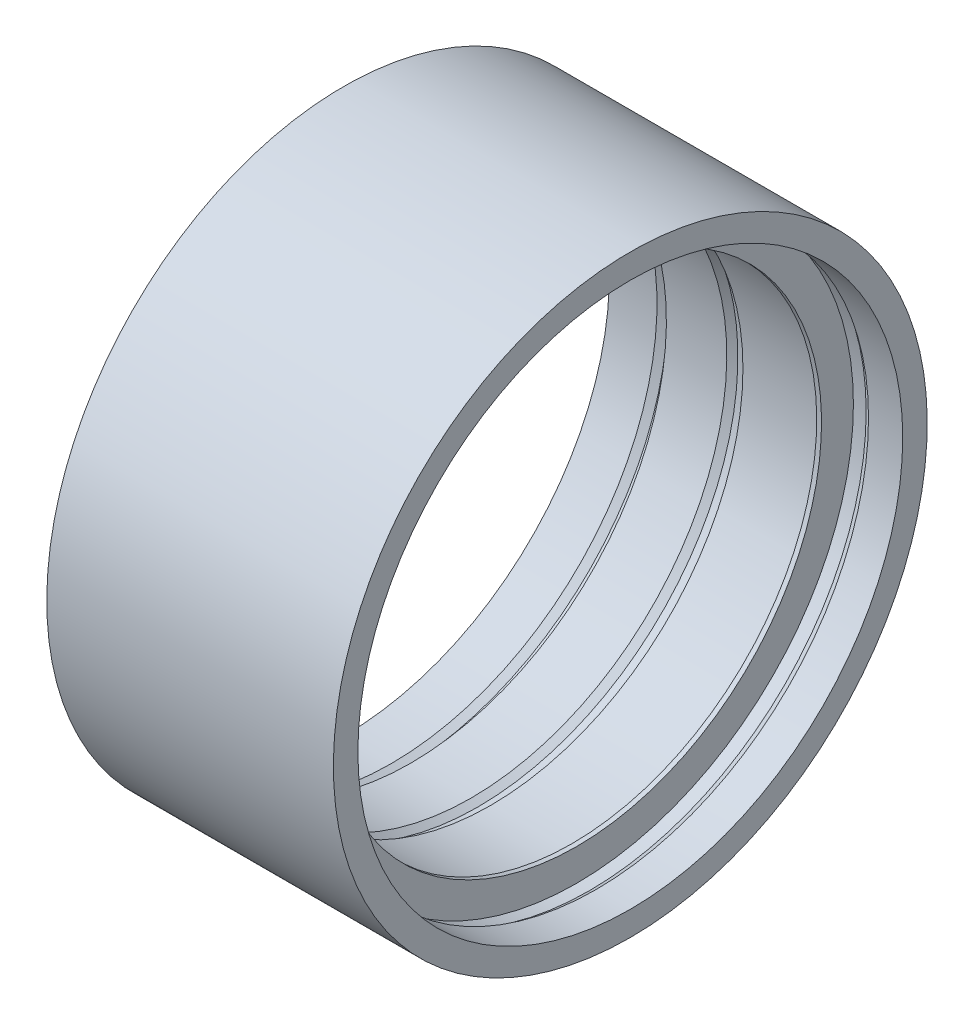
SolidWorks part; units mm, degrees
material "2018 slitina"
ref_plane "Přední rovina" through (0, 0, 0) normal (0, 0, 1) x (1, 0, 0)
ref_plane "Horní rovina" through (0, 0, 0) normal (0, 1, 0) x (1, 0, 0)
ref_plane "Pravá rovina" through (0, 0, 0) normal (1, 0, 0) x (0, 0, -1)
sketch "Skica2" plane through (0, 0, 0) normal (0, 0, 1) x (1, 0, 0)
  line L0 (-36.7133, -44.25) -> (6, -44.25)
  line L1 (6, -44.25) -> (6, -40.6)
  line L2 (6, -40.6) -> (0.9, -40.6)
  line L3 (-2, -36.5) -> (-2.7167, -36.5)
  line L4 (-2.7167, -36.5) -> (-2.8839, -37.6)
  line L5 (-2.8839, -37.6) -> (-14.8133, -37.6)
  line L6 (-14.8133, -37.6) -> (-14.8133, -38.75)
  line L7 (0, 0) -> (47.3772, 0) construction
  line L8 (-2, -36.5) -> (-2, -41.25)
  line L9 (-2, -41.25) -> (-0.1, -41.25)
  line L10 (-0.1, -41.25) -> (0.9, -40.6)
  line L11 (-14.8133, -38.75) -> (-16.7133, -38.75)
  line L12 (-16.7133, -38.75) -> (-17.7133, -38.094)
  line L13 (-17.7133, -38.094) -> (-26.7133, -38.094)
  line L14 (-26.7133, -38.094) -> (-26.7133, -40.25)
  line L15 (-26.7133, -40.25) -> (-28.6133, -40.25)
  line L16 (-28.6133, -40.25) -> (-29.6133, -39.594)
  line L17 (-29.6133, -39.594) -> (-36.7133, -39.594)
  line L18 (-36.7133, -39.594) -> (-36.7133, -44.25)
  line L19 (6, -40.6) -> (19.622, -44.25) construction
  line L20 (19.622, -44.25) -> (6, -44.25) construction
  arc A0 (-2.8691, -37.5) -> (-2.8691, 37.5) centre (-246.5, 0) ccw construction
  arc A1 (-2.8691, -37.5) -> (-2.8691, 37.5) centre (-246.5, 0) ccw construction
  point P0 (-15.7633, -38.75)
  point P11 (-2.8003, -37.05)
  dimension "D6" = 6
  dimension "D1" = 0.1
  dimension "D2" = 81.2
  dimension "D3" = 82.5
  dimension "D4" = 1.9
  dimension "D5" = 2.9
  dimension "D7" = 8
  dimension "D8" = 73
  dimension "D9" = 1.9
  dimension "D10" = 2.9
  dimension "D11" = 2
  dimension "D12" = 76.188
  dimension "D13" = 11
  dimension "D14" = 77.5
  dimension "D15" = 1.9
  dimension "D16" = 2.9
  dimension "D17" = 10
  dimension "D18" = 80.5
  dimension "D19" = 79.188
  dimension "D20" = 4
  dimension "D21" = 15
revolve "Rotovat1" add sketch "Skica2" angle 360 about L7
cosmetic thread "Kosmetický závit1" parameters "D2"=82
cosmetic thread "Kosmetický závit4" parameters "D2"=78
cosmetic thread "Kosmetický závit5" parameters "D2"=80
